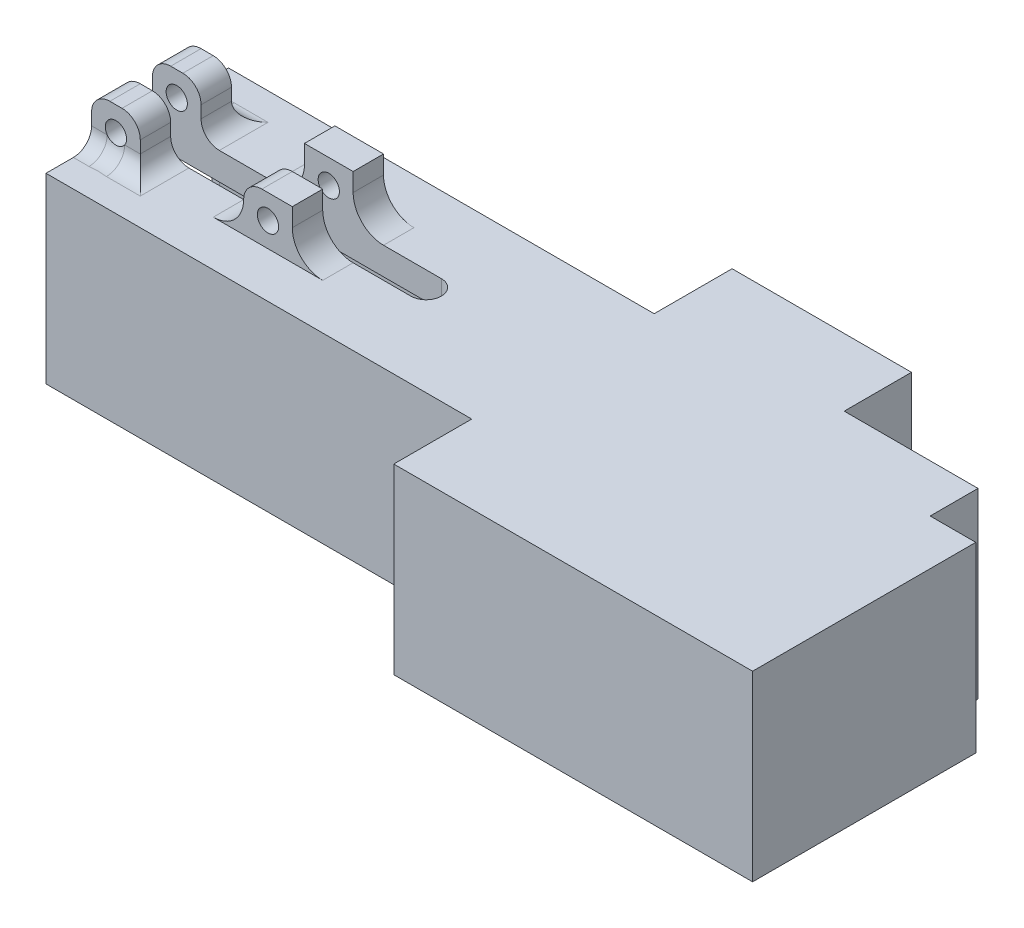
SolidWorks part; units mm, degrees
ref_plane "Front Plane" through (0, 0, 0) normal (0, 0, 1) x (1, 0, 0)
ref_plane "Top Plane" through (0, 0, 0) normal (0, 1, 0) x (1, 0, 0)
ref_plane "Right Plane" through (0, 0, 0) normal (1, 0, 0) x (0, 0, -1)
sketch "Sketch1" plane through (0, 0, 0) normal (0, 1, 0) x (1, 0, 0)
  line L0 (-36.2601, 15) -> (-106.2601, 15)
  line L1 (-106.2601, 15) -> (-106.2601, -15)
  line L2 (-106.2601, -15) -> (-36.2601, -15)
  line L4 (-36.2601, 15) -> (-36.2601, 27.8151)
  line L5 (22.7399, -27.8151) -> (-36.2601, -27.8151)
  line L6 (22.7399, -27.8151) -> (22.7399, 8.8843)
  line L7 (-6.7601, 27.8151) -> (-36.2601, 27.8151)
  line L8 (-36.2601, -27.8151) -> (-36.2601, -15)
  line L9 (-106.2601, 0) -> (0, 0) construction
  line L10 (-6.7601, 27.8151) -> (-6.7601, 16.75)
  line L11 (-6.7601, 16.75) -> (15.2399, 16.75)
  line L12 (15.2399, 16.75) -> (15.2399, 8.8843)
  line L13 (15.2399, 8.8843) -> (22.7399, 8.8843)
  point P6 (15.2399, 8.8843)
  dimension "D1" = 30
  dimension "D2" = 70
extrude "Boss-Extrude1" add sketch "Sketch1" along normal blind 30
sketch "Sketch5" plane through (-106.2601, 0, 0) normal (-1, 0, 0) x (0, 0, 1)
  line L0 (-9, 4.5) -> (9, 4.5)
  line L1 (10.5, 6) -> (10.5, 24)
  line L2 (9, 25.5) -> (-9, 25.5)
  line L3 (-10.5, 24) -> (-10.5, 6)
  line L12 (-9, 5) -> (9, 5)
  line L13 (10, 6) -> (10, 24)
  line L14 (9, 25) -> (-9, 25)
  line L15 (-10, 24) -> (-10, 6)
  line L16 (-9, 5) -> (9, 5) construction
  line L17 (10, 6) -> (10, 24) construction
  line L18 (9, 25) -> (-9, 25) construction
  line L19 (-10, 24) -> (-10, 6) construction
  arc A0 (9, 4.5) -> (10.5, 6) centre (9, 6) ccw
  arc A1 (10.5, 24) -> (9, 25.5) centre (9, 24) ccw
  arc A2 (-9, 25.5) -> (-10.5, 24) centre (-9, 24) ccw
  arc A3 (-10.5, 6) -> (-9, 4.5) centre (-9, 6) ccw
  arc A4 (-10, 6) -> (-9, 5) centre (-9, 6) ccw
  arc A5 (9, 5) -> (10, 6) centre (9, 6) ccw
  arc A6 (10, 24) -> (9, 25) centre (9, 24) ccw
  arc A7 (-9, 25) -> (-10, 24) centre (-9, 24) ccw
  arc A8 (-10, 6) -> (-9, 5) centre (-9, 6) ccw construction
  arc A9 (9, 5) -> (10, 6) centre (9, 6) ccw construction
  arc A10 (10, 24) -> (9, 25) centre (9, 24) ccw construction
  arc A11 (-9, 25) -> (-10, 24) centre (-9, 24) ccw construction
  dimension "D2" = 0
extrude "Cut-Extrude4" cut sketch "Sketch5" against normal blind 65
sketch "Sketch6" plane through (0, 30, 0) normal (0, 1, 0) x (1, 0, 0)
  line L0 (-106.2601, 15) -> (-106.2601, -15) construction
  line L1 (-106.2601, 2.5) -> (-58.7501, 2.5)
  line L2 (-106.2601, 2.5) -> (-106.2601, -2.5)
  line L3 (-106.2601, -2.5) -> (-58.7601, -2.5)
  line L4 (-56.2601, 0.01) -> (-56.2601, 0)
  arc A0 (-56.2601, 0) -> (-58.7601, -2.5) centre (-58.7601, 0) cw
  arc A1 (-58.7501, 2.5) -> (-56.2601, 0.01) centre (-58.7501, 0.01) cw
  point P6 (-106.2601, 0)
  point P9 (-56.2601, -2.5)
  point P12 (-56.2601, 2.5)
  dimension "D3" = 2.5
  dimension "D4" = 2.49
  dimension "D1" = 5
  dimension "D2" = 50
extrude "Cut-Extrude5" cut sketch "Sketch6" against normal blind 10
sketch "Sketch7" plane through (0, 30, 0) normal (0, 1, 0) x (1, 0, 0)
  line L1 (-106.2601, 2.5) -> (-98.2601, 2.5)
  line L2 (-106.2601, 2.5) -> (-106.2601, 7.5)
  line L3 (-106.2601, 7.5) -> (-98.2601, 7.5)
  line L4 (-98.2601, 2.5) -> (-98.2601, 7.5)
  line L5 (-106.2601, -2.5) -> (-98.2601, -2.5)
  line L6 (-106.2601, -2.5) -> (-106.2601, -7.5)
  line L7 (-106.2601, -7.5) -> (-98.2601, -7.5)
  line L8 (-98.2601, -2.5) -> (-98.2601, -7.5)
  dimension "D1" = 5
  dimension "D2" = 8
extrude "Boss-Extrude3" add sketch "Sketch7" along normal blind 8
sketch "Sketch8" plane through (0, 0, 7.5) normal (0, 0, 1) x (1, 0, 0)
  line L0 (-102.2601, 38) -> (-102.2601, 30) construction
  line L1 (-106.2601, 38) -> (-98.2601, 38) construction
  line L2 (-106.2601, 30) -> (-98.2601, 30) construction
  line L3 (-102.2601, 30) -> (-106.2601, 34) construction
  line L4 (-106.2601, 38) -> (-106.2601, 30) construction
  line L5 (-106.2601, 34) -> (-98.2601, 34) construction
  line L6 (-98.2601, 38) -> (-98.2601, 30) construction
  circle A0 centre (-102.2601, 34) radius 1.75
  dimension "D1" = 3.5
extrude "Cut-Extrude6" cut sketch "Sketch8" against normal blind 38
fillet "Fillet2" radius 3 2 edges at (-102.2601, 30, -7.5) (-102.2601, 30, 7.5)
fillet "Fillet3" radius 3 4 edges at (-106.2601, 38, 5) (-98.2601, 38, 5) (-106.2601, 38, -5) (-98.2601, 38, -5)
fillet "Fillet4" radius 3 11 edges at (-106.2601, 25.5, 5.75) (-106.2601, 25.0607, 10.0607) (-106.2601, 15, 10.5) (-106.2601, 4.9393, 10.0607) (-106.2601, 4.5, 0) (-106.2601, 4.9393, -10.0607) (-106.2601, 15, -10.5) (-106.2601, 25.0607, -10.0607) (-106.2601, 25.5, -5.75) (-98.2601, 30, 6.5) (-98.2601, 30, -6.5)
pattern_linear "LPattern1" count 2 spacing 25 along (1, 0, 0) of "Boss-Extrude3", "Cut-Extrude6"
fillet "Fillet5" radius 5 4 edges at (-73.2601, 30, -5) (-73.2601, 30, 5) (-81.2601, 30, -5) (-81.2601, 30, 5)
fillet "Fillet6" radius 3 1 edges at (-81.2601, 38, 5)
